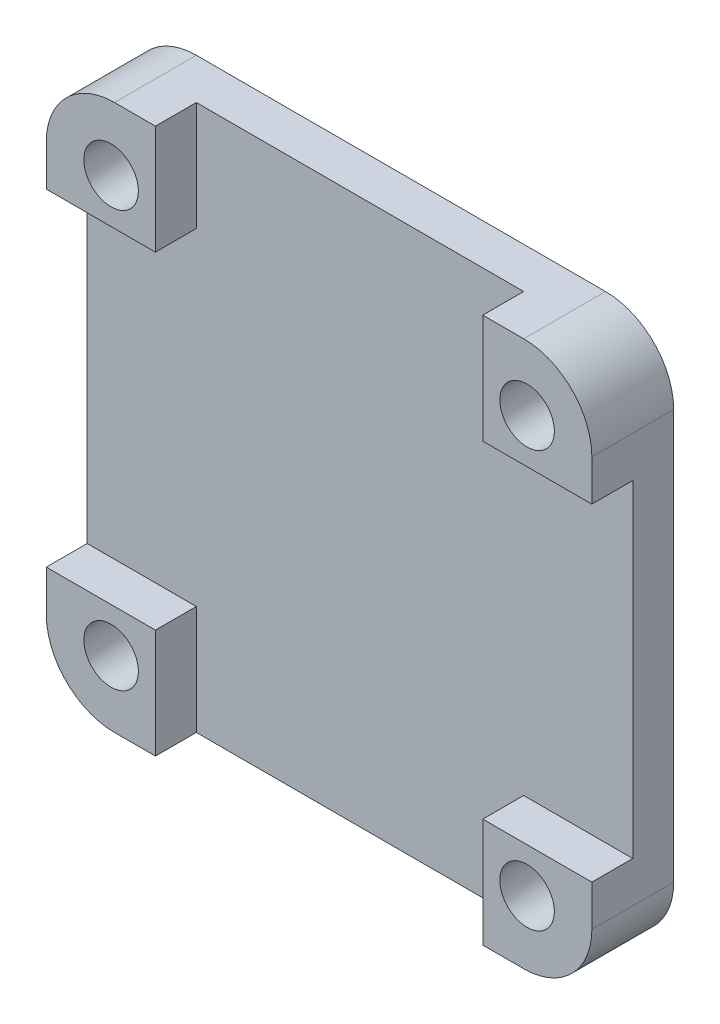
SolidWorks part; units mm, degrees
ref_plane "前视基准面" through (0, 0, 0) normal (0, 0, 1) x (1, 0, 0)
ref_plane "上视基准面" through (0, 0, 0) normal (0, 1, 0) x (1, 0, 0)
ref_plane "右视基准面" through (0, 0, 0) normal (1, 0, 0) x (0, 0, -1)
sketch "草图1" plane through (0, 0, 0) normal (0, 0, 1) x (1, 0, 0)
  line L0 (0, 0) -> (50.902, 0) construction
  line L1 (0, 0) -> (0, 39.4902) construction
  line L2 (-15, 20) -> (15, 20)
  line L3 (-20, 15) -> (-20, -15)
  line L4 (20, 15) -> (20, -15)
  line L5 (-15, -20) -> (15, -20)
  arc A0 (-15, 20) -> (-20, 15) centre (-15, 15) ccw
  arc A3 (15, 20) -> (20, 15) centre (15, 15) cw
  arc A4 (15, -20) -> (20, -15) centre (15, -15) ccw
  arc A7 (-15, -20) -> (-20, -15) centre (-15, -15) cw
  circle A8 centre (-15.25, 15.25) radius 2
  circle A9 centre (15.25, 15.25) radius 2
  circle A10 centre (15.25, -15.25) radius 2
  circle A11 centre (-15.25, -15.25) radius 2
  point P9 (0, -20)
  point P14 (-20, 0)
  point P15 (0, 20)
  point P23 (20, 0)
  dimension "D3" = 5
  dimension "D4" = 4
  dimension "D1" = 20
  dimension "D2" = 20
  dimension "D5" = 15.25
  dimension "D6" = 15.25
extrude "凸台-拉伸1" add sketch "草图1" along normal blind 3
sketch "草图2" plane through (0, 0, 3) normal (0, 0, 1) x (1, 0, 0)
  line L0 (0, 0) -> (46.7376, 0) construction
  line L1 (0, 0) -> (0, 23.4766) construction
  line L2 (-20, 15) -> (-20, 12)
  line L3 (-20, 15) -> (-20, -15) construction
  line L4 (-20, 12) -> (-12, 12)
  line L5 (-12, 12) -> (-12, 20)
  line L6 (15, 20) -> (-15, 20) construction
  line L7 (-12, 20) -> (-15, 20)
  line L8 (12, 20) -> (15, 20)
  line L9 (12, 12) -> (12, 20)
  line L10 (20, 12) -> (12, 12)
  line L11 (20, 15) -> (20, 12)
  line L12 (20, -15) -> (20, -12)
  line L13 (20, -12) -> (12, -12)
  line L14 (12, -12) -> (12, -20)
  line L15 (12, -20) -> (15, -20)
  line L16 (-12, -20) -> (-15, -20)
  line L17 (-12, -12) -> (-12, -20)
  line L18 (-20, -12) -> (-12, -12)
  line L19 (-20, -15) -> (-20, -12)
  arc A0 (-20, 15) -> (-15, 20) centre (-15, 15) cw
  arc A3 (20, 15) -> (15, 20) centre (15, 15) ccw
  arc A4 (20, -15) -> (15, -20) centre (15, -15) cw
  arc A7 (-20, -15) -> (-15, -20) centre (-15, -15) ccw
  circle A8 centre (-15.25, 15.25) radius 2
  circle A9 centre (15.25, 15.25) radius 2
  circle A10 centre (15.25, -15.25) radius 2
  circle A11 centre (-15.25, -15.25) radius 2
  dimension "D1" = 12
  dimension "D2" = 12
extrude "凸台-拉伸2" add sketch "草图2" along normal blind 3
sketch "草图3" plane through (0, 0, 0) normal (0, 0, -1) x (-1, 0, 0)
  line L0 (0, 0) -> (49.1095, 0) construction
  line L1 (0, 0) -> (0, 21.3742) construction
  line L2 (-13.5, 10) -> (-12, 10)
  line L3 (-12, 10) -> (-12, -10)
  line L4 (-13.5, 10) -> (-13.5, -10)
  line L5 (-13.5, -10) -> (-12, -10)
  line L6 (13.5, -10) -> (12, -10)
  line L7 (13.5, 10) -> (13.5, -10)
  line L8 (12, 10) -> (12, -10)
  line L9 (13.5, 10) -> (12, 10)
  point P9 (-13.5, 0)
  point P10 (-12, 0)
  dimension "D1" = 12
  dimension "D2" = 1.5
  dimension "D3" = 10
extrude "凸台-拉伸4" add sketch "草图3" along normal blind 3
sketch "草图5" plane through (0, 0, -3) normal (0, 0, -1) x (-1, 0, 0)
  line L1 (-13.5, 10) -> (-12, 10)
  line L2 (-13.5, 10) -> (-13.5, -10)
  line L3 (-13.5, -10) -> (-12, -10)
  line L4 (-12, 10) -> (-12, -10)
revolve "旋转2" add sketch "草图5" angle 90 about L4 reverse direction yes
sketch "草图6" plane through (12, 0, 0) normal (-1, 0, 0) x (0, 0, 1)
  line L0 (-4.5, 10) -> (0, 10) construction
  line L1 (-4.5, -10) -> (-3, -10)
  line L2 (-4.5, -10) -> (-4.5, 10)
  line L3 (-4.5, 10) -> (-3, 10)
  line L4 (-3, -10) -> (-3, 10)
  dimension "D1" = 1.5
extrude "凸台-拉伸5" add sketch "草图6" along normal blind 5
sketch "草图8" plane through (0, 0, -3) normal (0, 0, -1) x (-1, 0, 0)
  line L1 (13.5, 10) -> (12, 10)
  line L2 (13.5, 10) -> (13.5, -10)
  line L3 (13.5, -10) -> (12, -10)
  line L4 (12, 10) -> (12, -10)
revolve "旋转3" add sketch "草图8" angle 90 about L4
sketch "草图9" plane through (-12, 0, 0) normal (1, 0, 0) x (0, 0, -1)
  line L0 (4.5, -10) -> (0, -10) construction
  line L1 (4.5, 10) -> (3, 10)
  line L2 (4.5, 10) -> (4.5, -10)
  line L3 (4.5, -10) -> (3, -10)
  line L4 (3, 10) -> (3, -10)
  dimension "D1" = 1.5
extrude "凸台-拉伸6" add sketch "草图9" along normal blind 5
